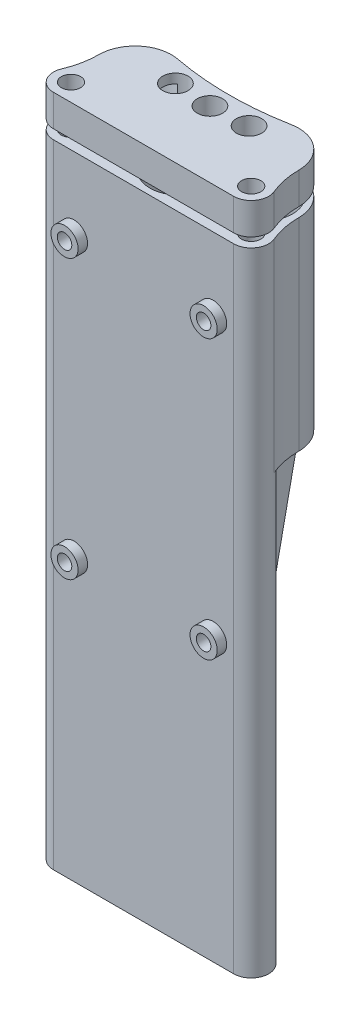
SolidWorks part; units mm, degrees
ref_plane "Front Plane" through (0, 0, 0) normal (0, 0, 1) x (1, 0, 0)
ref_plane "Top Plane" through (0, 0, 0) normal (0, 1, 0) x (1, 0, 0)
ref_plane "Right Plane" through (0, 0, 0) normal (1, 0, 0) x (0, 0, -1)
sketch "Sketch1" plane through (0, 0, 0) normal (0, 1, 0) x (1, 0, 0)
  line L0 (-28.5, 0) -> (28.5, 0) construction
  line L1 (-28.5, 0) -> (28.5, 0) construction
  line L2 (-28.5, 5.55) -> (28.5, 5.55)
  line L3 (-28.5, -5.55) -> (28.5, -5.55)
  circle A0 centre (-28.5, 0) radius 3.05
  circle A1 centre (28.5, 0) radius 3.05
  arc A2 (-28.5, 5.55) -> (-28.5, -5.55) centre (-28.5, 0) ccw
  arc A3 (28.5, -5.55) -> (28.5, 5.55) centre (28.5, 0) ccw
  point P4 (0, 0)
  dimension "D1" = 6.1
  dimension "D2" = 2.5
  dimension "D3" = 57
extrude "Boss-Extrude1" add sketch "Sketch1" along normal mid plane 200
sketch "Sketch2" plane through (0, 0, 0) normal (1, 0, 0) x (0, 0, -1)
  line L0 (5.55, 36.6649) -> (5.55, -0.5321)
  line L1 (5.55, 100) -> (5.55, -100) construction
  line L2 (5.55, -0.5321) -> (7.05, -0.5321)
  line L3 (7.05, -0.5321) -> (14.8208, 36.6649)
  line L4 (14.8208, 36.6649) -> (5.55, 36.6649)
  dimension "D1" = 11.8
  dimension "D2" = 38
  dimension "D3" = 1.5
extrude "Boss-Extrude2" add sketch "Sketch2" along normal up to vertex (28.5 mm away) and the other way up to vertex (28.5 mm away) up to point (28.5, 100, -5.55) other way up to point (-28.5, 100, -5.55)
sketch "Sketch3" plane through (0, -1.4335, -6.8617) normal (0, -0.2045, -0.9789) x (-1, 0, 0)
  line L0 (-14, 33.9209) -> (14, 5.9209) construction
  line L1 (0, 11.204) -> (0, -11.204) construction
  line L3 (-28.5, 0.9209) -> (-28.5, 38.9209) construction
  circle A0 centre (-14, 33.9209) radius 1.5
  circle A1 centre (-14, 5.9209) radius 1.5
  circle A2 centre (14, 33.9209) radius 1.5
  circle A3 centre (14, 5.9209) radius 1.5
  circle A4 centre (-14, 33.9209) radius 2.5
  circle A5 centre (14, 33.9209) radius 2.5
  circle A6 centre (14, 5.9209) radius 2.5
  circle A7 centre (-14, 5.9209) radius 2.5
  point P8 (0, 19.9209)
  point P13 (-28.5, 19.9209)
  dimension "D1" = 3
  dimension "D2" = 28
  dimension "D3" = 28
  dimension "D4" = 1
extrude "Boss-Extrude3" add sketch "Sketch3" along normal blind 1.5
chamfer "Chamfer1" distance 0.5 angle 45 4 edges at (14, 6.5027, -10.052) (-14, 6.5027, -10.052) (-14, 33.911, -15.7779) (14, 33.911, -15.7779)
sketch "Sketch6" plane through (0, 100, 0) normal (0, 1, 0) x (1, 0, 0)
  line L0 (-28.5, -5.55) -> (28.5, -5.55) construction
  line L3 (0, -17.5762) -> (0, 17.5762) construction
  line L4 (-28.5, -5.55) -> (28.5, -5.55)
  arc A0 (-3.9104, 14.6079) -> (3.9104, 14.6079) centre (0, 5.95) ccw
  arc A1 (-14.1587, 19.2894) -> (-10.6457, 12.3022) centre (-20.1375, 11.9067) ccw
  arc A2 (10.6457, 12.3022) -> (14.1587, 19.2894) centre (20.1375, 11.9067) ccw
  circle A4 centre (0, 5.95) radius 11.5 construction
  circle A6 centre (-20.1375, 11.9067) radius 11.5 construction
  circle A7 centre (20.1375, 11.9067) radius 11.5 construction
  circle A8 centre (-28.5, 0) radius 3.05 construction
  circle A10 centre (28.5, 0) radius 3.05 construction
  arc A11 (-31.6375, 11.9067) -> (-33.6123, 2.1604) centre (-56.6757, 11.9067) cw
  arc A12 (-28.5, 5.55) -> (-28.5, -5.55) centre (-28.5, 0) ccw construction
  arc A13 (-31.6375, 11.9067) -> (-17.9882, 23.2041) centre (-20.1375, 11.9067) cw
  arc A14 (31.6375, 11.9067) -> (17.9882, 23.2041) centre (20.1375, 11.9067) ccw
  arc A15 (31.6375, 11.9067) -> (33.6123, 2.1604) centre (56.6757, 11.9067) ccw
  arc A16 (28.5, -5.55) -> (28.5, 5.55) centre (28.5, 0) ccw construction
  arc A17 (-17.9882, 23.2041) -> (17.9882, 23.2041) centre (0, 117.7561) ccw
  arc A18 (-10.6457, 12.3022) -> (-14.1587, 19.2894) centre (-11.6498, 16.1741) ccw
  arc A19 (3.9104, 14.6079) -> (-3.9104, 14.6079) centre (0, 15.45) ccw
  arc A20 (14.1587, 19.2894) -> (10.6457, 12.3022) centre (11.6498, 16.1741) ccw
  circle A21 centre (-11.6498, 16.1741) radius 6 construction
  circle A22 centre (-11.6498, 16.1741) radius 4 construction
  circle A23 centre (-20.1375, 11.9067) radius 9.5 construction
  circle A24 centre (0, 5.95) radius 9.5 construction
  circle A25 centre (20.1375, 11.9067) radius 9.5 construction
  arc A26 (-33.6123, 2.1604) -> (-28.5, -5.55) centre (-28.5, 0) ccw
  arc A27 (33.6123, 2.1604) -> (28.5, -5.55) centre (28.5, 0) cw
  circle A28 centre (-28.5, 0) radius 3.05
  circle A29 centre (28.5, 0) radius 3.05
  line M6 (28.5, 5.55) -> (-28.5, 5.55)
  dimension "D1" = 19
  dimension "D4" = 8
  dimension "D2" = 2
  dimension "D3" = 2
  dimension "D5" = 2
extrude "Boss-Extrude5" add sketch "Sketch6" against normal blind 60
extrude "Cut-Extrude2" cut sketch "Sketch6<2>" against normal up to surface (60 mm away) contours A1 M6 | A0 M6 | A2 M6 region at (20.1375, 100, -4.273) region at (-20.1375, 100, -4.273) region at (0, 100, -1.7011) up to face at (0, 40, -11.9943)
sketch "Sketch6<2>" plane through (0, 100, 0) normal (0, 1, 0) x (1, 0, 0) same geometry as "Sketch6"
sketch "Sketch7" plane through (0, 40, 0) normal (0, -1, 0) x (1, 0, 0)
  line L0 (-28.5, -5.55) -> (28.5, -5.55)
  line L4 (-9.4916, -5.55) -> (-13.0776, -5.55)
  line L5 (-27.1973, -5.55) -> (-28.5, -5.55)
  line L6 (28.5, -5.55) -> (27.1973, -5.55)
  line L7 (13.0776, -5.55) -> (9.4916, -5.55)
  arc A16 (-10.6457, -12.3022) -> (-13.0776, -5.55) centre (-20.1375, -11.9067) ccw
  arc A17 (-14.1587, -19.2894) -> (-10.6457, -12.3022) centre (-11.6498, -16.1741) ccw
  arc A18 (-27.1973, -5.55) -> (-14.1587, -19.2894) centre (-20.1375, -11.9067) ccw
  arc A20 (-31.6375, -11.9067) -> (-33.6123, -2.1604) centre (-56.6757, -11.9067) ccw
  arc A21 (-31.6375, -11.9067) -> (-17.9882, -23.2041) centre (-20.1375, -11.9067) ccw
  arc A22 (17.9882, -23.2041) -> (-17.9882, -23.2041) centre (0, -117.7561) ccw
  arc A23 (17.9882, -23.2041) -> (31.6375, -11.9067) centre (20.1375, -11.9067) ccw
  arc A24 (33.6123, -2.1604) -> (31.6375, -11.9067) centre (56.6757, -11.9067) ccw
  arc A26 (14.1587, -19.2894) -> (27.1973, -5.55) centre (20.1375, -11.9067) ccw
  arc A27 (10.6457, -12.3022) -> (14.1587, -19.2894) centre (11.6498, -16.1741) ccw
  arc A28 (13.0776, -5.55) -> (10.6457, -12.3022) centre (20.1375, -11.9067) ccw
  arc A29 (3.9104, -14.6079) -> (9.4916, -5.55) centre (0, -5.95) ccw
  arc A30 (-3.9104, -14.6079) -> (3.9104, -14.6079) centre (0, -15.45) ccw
  arc A31 (-9.4916, -5.55) -> (-3.9104, -14.6079) centre (0, -5.95) ccw
  arc A36 (-31.6375, -11.9067) -> (-33.6123, -2.1604) centre (-56.6757, -11.9067) ccw
  arc A37 (-31.6375, -11.9067) -> (-17.9882, -23.2041) centre (-20.1375, -11.9067) ccw
  arc A38 (17.9882, -23.2041) -> (-17.9882, -23.2041) centre (0, -117.7561) ccw
  arc A39 (17.9882, -23.2041) -> (31.6375, -11.9067) centre (20.1375, -11.9067) ccw
  arc A40 (33.6123, -2.1604) -> (31.6375, -11.9067) centre (56.6757, -11.9067) ccw
  arc A48 (-33.6123, -2.1604) -> (-28.5, -5.55) centre (-28.5, 0) ccw
  arc A49 (-33.6123, -2.1604) -> (-28.5, -5.55) centre (-28.5, 0) ccw
  arc A50 (28.5, -5.55) -> (33.6123, -2.1604) centre (28.5, 0) ccw
  arc A51 (28.5, -5.55) -> (33.6123, -2.1604) centre (28.5, 0) ccw
  dimension "D1" = 0
extrude "Boss-Extrude6" add sketch "Sketch7" along normal blind 4
extrude "Boss-Extrude7" add sketch "Sketch6<3>" along normal blind 7 from offset 3 separate body
sketch "Sketch6<3>" plane through (0, 100, 0) normal (0, 1, 0) x (1, 0, 0) same geometry as "Sketch6"
sketch "Sketch9" plane through (0, 110, 0) normal (0, 1, 0) x (1, 0, 0)
  line L1 (-28.5, -5.55) -> (28.5, -5.55)
  line L2 (-28.5, -5.55) -> (28.5, -5.55)
  circle A0 centre (-11.6498, 16.1741) radius 4
  circle A1 centre (0, 15.45) radius 4
  circle A2 centre (11.6498, 16.1741) radius 4
  arc A3 (14.1587, 19.2894) -> (10.6457, 12.3022) centre (11.6498, 16.1741) ccw construction
  arc A4 (3.9104, 14.6079) -> (-3.9104, 14.6079) centre (0, 15.45) ccw construction
  arc A5 (-10.6457, 12.3022) -> (-14.1587, 19.2894) centre (-11.6498, 16.1741) ccw construction
  circle A6 centre (28.5, 0) radius 3.05 construction
  arc A7 (-17.9882, 23.2041) -> (-31.6375, 11.9067) centre (-20.1375, 11.9067) ccw
  arc A8 (-33.6123, 2.1604) -> (-31.6375, 11.9067) centre (-56.6757, 11.9067) ccw
  arc A9 (-33.6123, 2.1604) -> (-28.5, -5.55) centre (-28.5, 0) ccw
  arc A10 (28.5, -5.55) -> (33.6123, 2.1604) centre (28.5, 0) ccw
  arc A11 (31.6375, 11.9067) -> (33.6123, 2.1604) centre (56.6757, 11.9067) ccw
  arc A12 (31.6375, 11.9067) -> (17.9882, 23.2041) centre (20.1375, 11.9067) ccw
  arc A13 (-17.9882, 23.2041) -> (17.9882, 23.2041) centre (0, 117.7561) ccw
  arc A14 (-17.9882, 23.2041) -> (-31.6375, 11.9067) centre (-20.1375, 11.9067) ccw
  arc A15 (-33.6123, 2.1604) -> (-31.6375, 11.9067) centre (-56.6757, 11.9067) ccw
  arc A16 (-33.6123, 2.1604) -> (-28.5, -5.55) centre (-28.5, 0) ccw
  arc A17 (28.5, -5.55) -> (33.6123, 2.1604) centre (28.5, 0) ccw
  arc A18 (31.6375, 11.9067) -> (33.6123, 2.1604) centre (56.6757, 11.9067) ccw
  arc A19 (31.6375, 11.9067) -> (17.9882, 23.2041) centre (20.1375, 11.9067) ccw
  arc A20 (-17.9882, 23.2041) -> (17.9882, 23.2041) centre (0, 117.7561) ccw
  circle A21 centre (-28.5, 0) radius 3.05 construction
  circle A22 centre (28.5, 0) radius 3.05
  circle A23 centre (-28.5, 0) radius 3.05
  dimension "D1" = 0
extrude "Boss-Extrude8" add sketch "Sketch9" along normal blind 3
sketch "Sketch4" plane through (0, 0, 5.55) normal (0, 0, 1) x (1, 0, 0)
  line L0 (0, -17.5762) -> (0, 17.5762) construction
  line L1 (-26, 100) -> (26, 100) construction
  line L2 (-26, 100) -> (-26, -15) construction
  line L3 (-26, -15) -> (26, -15) construction
  line L4 (26, 100) -> (26, -15) construction
  line L5 (-28.5, 100) -> (28.5, 100) construction
  line L6 (-22, 77) -> (22, 77) construction
  line L7 (-22, -11) -> (22, -11) construction
  circle A0 centre (-22, 77) radius 2.3
  circle A1 centre (22, 77) radius 2.3
  circle A2 centre (-22, -11) radius 2.3
  circle A3 centre (22, -11) radius 2.3
  circle A4 centre (-22, 77) radius 4.3
  circle A5 centre (22, 77) radius 4.3
  circle A6 centre (-22, -11) radius 4.3
  circle A7 centre (22, -11) radius 4.3
  point P4 (0, 100)
  point P12 (0, 77)
  point P16 (0, -11)
  dimension "D7" = 4.6
  dimension "D1" = 52
  dimension "D2" = 115
  dimension "D3" = 23
  dimension "D4" = 4
  dimension "D5" = 4
  dimension "D6" = 4
  dimension "D8" = 2
extrude "Boss-Extrude4" add sketch "Sketch4" along normal blind 3
extrude "Cut-Extrude1" cut sketch "Sketch4<2>" against normal blind 3 contours A1 | A0 | A3 | A2 region at (-22, 77, 5.55) region at (22, 77, 5.55) region at (-22, -11, 5.55) region at (22, -11, 5.55)
sketch "Sketch4<2>" plane through (0, 0, 5.55) normal (0, 0, 1) x (1, 0, 0) same geometry as "Sketch4"
sketch "Sketch10" plane through (0, 0, -5.55) normal (0, 0, -1) x (-1, 0, 0)
  line L0 (0, 17.5762) -> (0, -17.5762) construction
  line L1 (-24.5, -5.5321) -> (24.5, -5.5321) construction
  line L2 (-24.5, -5.5321) -> (-24.5, -63.5321) construction
  line L3 (-24.5, -63.5321) -> (24.5, -63.5321) construction
  line L4 (24.5, -5.5321) -> (24.5, -63.5321) construction
  line L5 (-28.5, -0.5321) -> (28.5, -0.5321) construction
  line L7 (-22.9123, -2.7821) -> (-26.0877, -2.7821)
  line L8 (-26.0877, -2.7821) -> (-27.6754, -5.5321)
  line L9 (-27.6754, -5.5321) -> (-26.0877, -8.2821)
  line L10 (-26.0877, -8.2821) -> (-22.9123, -8.2821)
  line L11 (-22.9123, -8.2821) -> (-21.3246, -5.5321)
  line L12 (-21.3246, -5.5321) -> (-22.9123, -2.7821)
  line L13 (26.0877, -2.7821) -> (22.9123, -2.7821)
  line L14 (22.9123, -2.7821) -> (21.3246, -5.5321)
  line L15 (21.3246, -5.5321) -> (22.9123, -8.2821)
  line L16 (22.9123, -8.2821) -> (26.0877, -8.2821)
  line L17 (26.0877, -8.2821) -> (27.6754, -5.5321)
  line L18 (27.6754, -5.5321) -> (26.0877, -2.7821)
  line L19 (-22.9123, -60.7821) -> (-26.0877, -60.7821)
  line L20 (-26.0877, -60.7821) -> (-27.6754, -63.5321)
  line L21 (-27.6754, -63.5321) -> (-26.0877, -66.2821)
  line L22 (-26.0877, -66.2821) -> (-22.9123, -66.2821)
  line L23 (-22.9123, -66.2821) -> (-21.3246, -63.5321)
  line L24 (-21.3246, -63.5321) -> (-22.9123, -60.7821)
  line L25 (22.9123, -60.7821) -> (21.3246, -63.5321)
  line L26 (21.3246, -63.5321) -> (22.9123, -66.2821)
  line L27 (22.9123, -66.2821) -> (26.0877, -66.2821)
  line L28 (26.0877, -66.2821) -> (27.6754, -63.5321)
  line L29 (27.6754, -63.5321) -> (26.0877, -60.7821)
  line L30 (26.0877, -60.7821) -> (22.9123, -60.7821)
  circle A0 centre (-24.5, -5.5321) radius 1.5
  circle A1 centre (24.5, -5.5321) radius 1.5
  circle A2 centre (24.5, -63.5321) radius 1.5
  circle A3 centre (-24.5, -63.5321) radius 1.5
  circle A4 centre (-24.5, -5.5321) radius 2.75 construction
  circle A5 centre (24.5, -5.5321) radius 2.75 construction
  circle A6 centre (-24.5, -63.5321) radius 2.75 construction
  circle A7 centre (24.5, -63.5321) radius 2.75 construction
  point P8 (0, -5.5321)
  point P13 (0, 0)
  dimension "D1" = 3
  dimension "D2" = 49
  dimension "D3" = 58
  dimension "D4" = 5
  dimension "D5" = 5.5
extrude "Cut-Extrude3" cut sketch "Sketch10" against normal blind 2
extrude "Cut-Extrude4" cut sketch "Sketch10<3>" against normal blind 8 contours A0 | A1 | A3 | A2 region at (24.5, -5.5321, -5.55) region at (-24.5, -5.5321, -5.55) region at (-24.5, -63.5321, -5.55) region at (24.5, -63.5321, -5.55)
sketch "Sketch10<3>" plane through (0, 0, -5.55) normal (0, 0, -1) x (-1, 0, 0) same geometry as "Sketch10"
